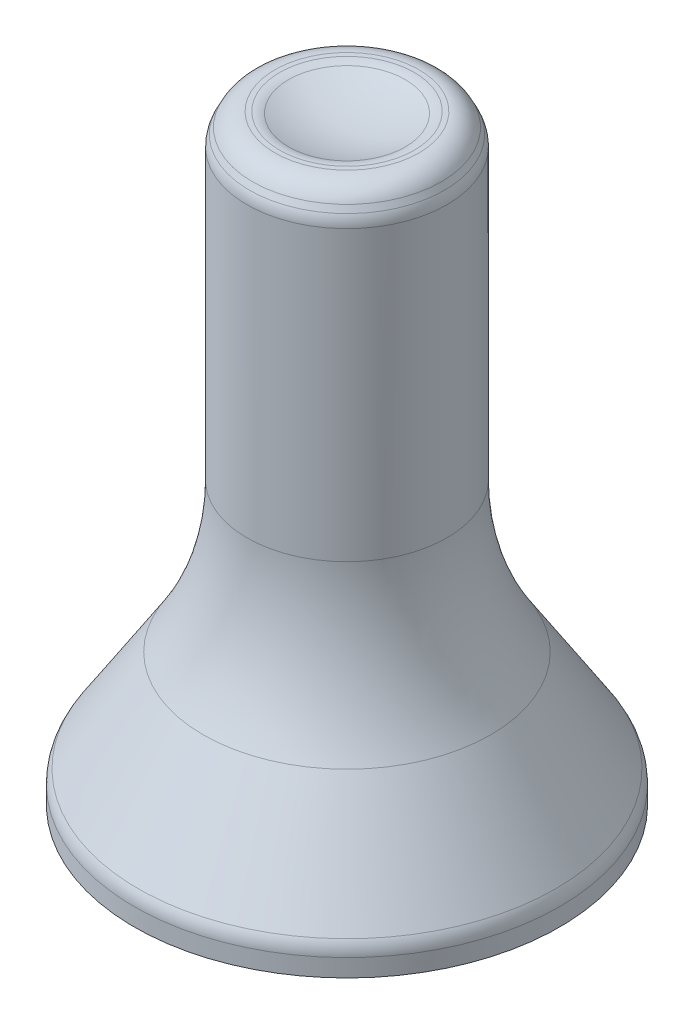
SolidWorks part; units mm, degrees
ref_plane "Front Plane" through (0, 0, 0) normal (0, 0, 1) x (1, 0, 0)
ref_plane "Top Plane" through (0, 0, 0) normal (0, 1, 0) x (1, 0, 0)
ref_plane "Right Plane" through (0, 0, 0) normal (1, 0, 0) x (0, 0, -1)
sketch "Sketch1" plane through (0, 0, 0) normal (0, 0, 1) x (1, 0, 0)
  line L0 (0, 0) -> (8.5, 0)
  line L1 (8.5, 0) -> (8.5, 1)
  line L2 (8.5, 1) -> (4, 8)
  line L3 (4, 8) -> (4, 23)
  line L4 (4, 23) -> (3.5, 24)
  line L5 (3.5, 24) -> (2.5, 24)
  line L6 (2.5, 24) -> (1.3, 23.5) construction
  line L7 (0, 23.5) -> (0, 0) construction
  line L8 (0, 0) -> (0, 23.5)
  line L9 (1.3, 23.5) -> (0, 23.5) construction
  spline S0 degree 2 poles (2.5, 24) (1.3, 23.5) (0, 23.5) knots 0 0 0 1 1 1
  dimension "D1" = 24
  dimension "D2" = 4
  dimension "D3" = 1
  dimension "D4" = 8
  dimension "D5" = 1
  dimension "D6" = 0.5
  dimension "D7" = 0.5
  dimension "D8" = 1
  dimension "D9" = 8.5
  dimension "D10" = 4
revolve "Revolve1" add sketch "Sketch1" angle 360 about L7
fillet "Fillet1" radius 11 1 edges at (-4, 8, 0)
fillet "Fillet2" radius 1 4 edges at (-2.5, 24, 0) (-3.5, 24, 0) (-4, 23, 0) (-8.5, 1, 0)
sketch "Sketch3" plane through (0, 0, 0) normal (0, 0, 1) x (1, 0, 0)
  line L0 (0, 0) -> (3.875, 0)
  line L1 (-8.5, 0) -> (8.5, 0) construction
  line L2 (3.875, 0) -> (3.875, 6.5)
  line L3 (3.875, 6.5) -> (3.05, 7.325)
  line L4 (3.05, 7.325) -> (3.05, 17.75)
  line L5 (3.05, 17.75) -> (0, 17.75)
  line L6 (0, 17.75) -> (0, 0)
  dimension "D1" = 17.75
  dimension "D2" = 3.875
  dimension "D3" = 45
  dimension "D4" = 3.05
  dimension "D5" = 6.5
revolve "Cut-Revolve1" cut sketch "Sketch3" angle 360 about L6
ref_plane "Plane1" through (0, 7.325, 0) normal (0, 1, 0) x (1, 0, 0)
sketch "Sketch4" plane through (0, 17.75, 0) normal (0, -1, 0) x (1, 0, 0)
  line L0 (-2.6557, 1.5) -> (2.6557, 1.5)
  line L5 (-999.8551, -3) -> (49000.1449, -3) construction
  arc A7 (-0.1, -3.0484) -> (0.1, -3.0484) centre (0, 0) ccw
  arc A9 (0.1, -3.0484) -> (-0.1, -3.0484) centre (0, -3.05) ccw
  arc A10 (2.6557, 1.5) -> (-2.6557, 1.5) centre (0, 0) ccw
  circle A11 centre (0, 0) radius 3.05 construction
  point P1 (-1.8297, 1.5)
  point P10 (0, 0)
  point P11 (0, 0)
  dimension "D1" = 3
  dimension "D3" = 0.2
  dimension "D2" = 4.5
extrude "Boss-Extrude1" add sketch "Sketch4" along normal up to surface (10.425 mm away) up to plane "Plane1"
chamfer "Chamfer1" distance 0.35 angle 45 1 edges at (0, 7.325, 1.5)
